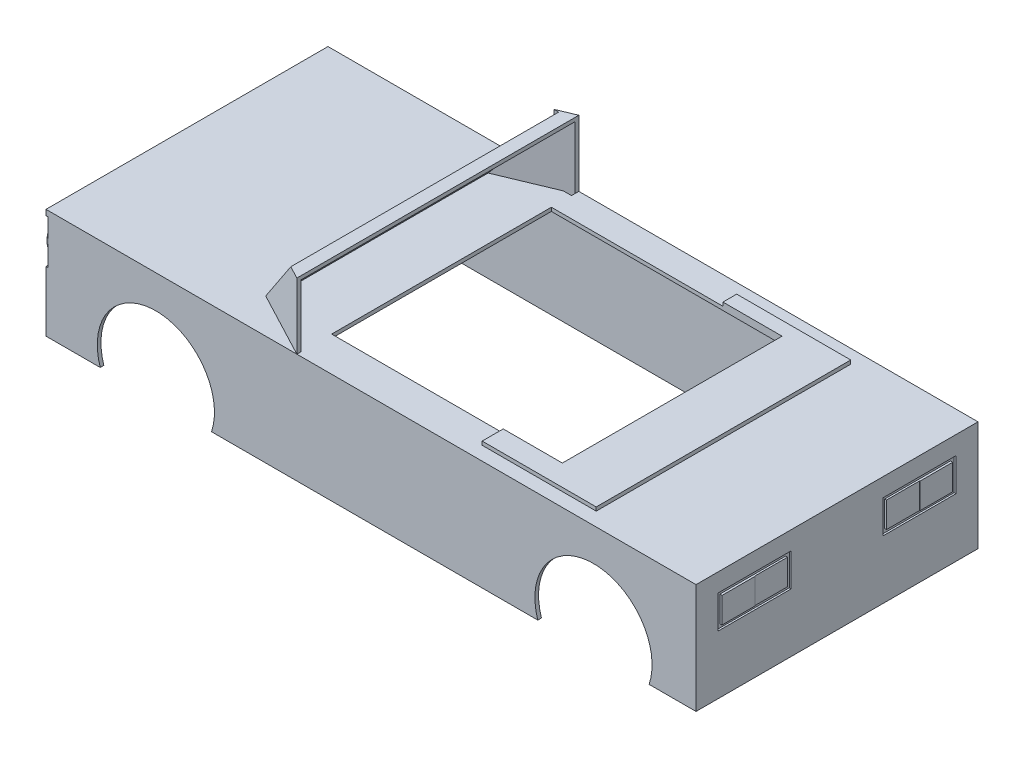
SolidWorks part; units mm, degrees
ref_plane "Front Plane" through (0, 0, 0) normal (0, 0, 1) x (1, 0, 0)
ref_plane "Top Plane" through (0, 0, 0) normal (0, 1, 0) x (1, 0, 0)
ref_plane "Right Plane" through (0, 0, 0) normal (1, 0, 0) x (0, 0, -1)
sketch "Sketch1" plane through (0, 0, 0) normal (0, 0, 1) x (1, 0, 0)
  line L1 (-88.75, 15) -> (88.75, 15)
  line L2 (-88.75, 15) -> (-88.75, -15)
  line L3 (-88.75, -15) -> (88.75, -15)
  line L4 (88.75, 15) -> (88.75, -15)
  point P0 (0, 0)
  dimension "D1" = 177.5
  dimension "D2" = 30
extrude "Boss-Extrude1" add sketch "Sketch1" along normal blind 77
sketch "Sketch2" plane through (0, -15, 0) normal (0, -1, 0) x (1, 0, 0)
  line L0 (-88.75, 77) -> (88.75, 77) construction
  line L1 (-87.75, 76) -> (87.75, 76)
  line L2 (-87.75, 76) -> (-87.75, 3)
  line L3 (-87.75, 3) -> (87.75, 3)
  line L4 (87.75, 76) -> (87.75, 3)
  line L5 (-88.75, 77) -> (-88.75, 0) construction
  dimension "D1" = 175.5
  dimension "D2" = 73
  dimension "D3" = 1
  dimension "D4" = 1
extrude "Cut-Extrude1" cut sketch "Sketch2" against normal blind 29
sketch "Sketch3" plane through (0, 0, 77) normal (0, 0, 1) x (1, 0, 0)
  line L0 (88.75, 15) -> (-88.75, 15) construction
  line L1 (-88.75, 15) -> (-88.75, -15) construction
  line L2 (88.75, -15) -> (88.75, 15) construction
  circle A0 centre (-58.75, -10) radius 16
  circle A1 centre (60.75, -10) radius 16
  dimension "D1" = 32
  dimension "D2" = 25
  dimension "D3" = 25
  dimension "D4" = 30
  dimension "D5" = 28
extrude "Cut-Extrude2" cut sketch "Sketch3" against normal blind 1
sketch "Sketch4" plane through (0, 0, 0) normal (0, 0, -1) x (-1, 0, 0)
  line L0 (-88.75, 15) -> (88.75, 15) construction
  line L1 (88.75, 15) -> (88.75, -15) construction
  line L2 (-88.75, -15) -> (-88.75, 15) construction
  circle A0 centre (-60.75, -10) radius 16
  circle A1 centre (58.75, -10) radius 16
  dimension "D1" = 25
  dimension "D2" = 25
  dimension "D3" = 30
  dimension "D4" = 28
extrude "Cut-Extrude3" cut sketch "Sketch4" against normal blind 1
sketch "Sketch5" plane through (0, 15, 0) normal (0, 1, 0) x (1, 0, 0)
  line L1 (-20.25, -7.5) -> (42.75, -7.5)
  line L2 (-20.25, -7.5) -> (-20.25, -67.5)
  line L3 (-20.25, -67.5) -> (42.75, -67.5)
  line L4 (42.75, -7.5) -> (42.75, -67.5)
  line L5 (88.75, 0) -> (-88.75, 0) construction
  line L7 (88.75, -77) -> (88.75, 0) construction
  point P0 (11.25, -35)
  dimension "D1" = 63
  dimension "D2" = 60
  dimension "D3" = 7.5
  dimension "D4" = 46
extrude "Cut-Extrude4" cut sketch "Sketch5" against normal blind 1
sketch "Sketch6" plane through (0, 15, 0) normal (0, 1, 0) x (1, 0, 0)
  line L0 (88.75, 0) -> (-88.75, 0) construction
  line L1 (-20.25, 0) -> (-38.25, 0)
  line L2 (-20.25, 0) -> (-20.25, -77)
  line L3 (-20.25, -77) -> (-38.25, -77)
  line L4 (-38.25, 0) -> (-38.25, -77)
  line L5 (88.75, -77) -> (-88.75, -77) construction
  line L6 (-20.25, -7.5) -> (-20.25, -67.5) construction
  dimension "D1" = 18
extrude "Boss-Extrude2" add sketch "Sketch6" along normal blind 18
sketch "Sketch9" plane through (0, 33, 0) normal (0, 1, 0) x (1, 0, 0)
  line L0 (-20.25, 0) -> (-38.25, -7.5)
  line L1 (-38.25, 0) -> (-38.25, -77) construction
  line L2 (-38.25, -7.5) -> (-38.25, 0)
  line L3 (-38.25, 0) -> (-20.25, 0)
  line L4 (-20.25, -77) -> (-38.25, -77)
  line L5 (-38.25, -77) -> (-38.25, -67.5)
  line L6 (-38.25, 0) -> (-38.25, -77) construction
  line L7 (-38.25, -67.5) -> (-20.25, -77)
  dimension "D1" = 7.5
extrude "Cut-Extrude6" cut sketch "Sketch9" against normal blind 18
sketch "Sketch12" plane through (0, 0, 77) normal (0, 0, 1) x (1, 0, 0)
  line L0 (-23.75, 33) -> (-38.25, 15)
  line L1 (-20.25, 33) -> (-38.25, 33) construction
  line L2 (-38.25, 15) -> (-38.25, 33)
  line L3 (-38.25, 33) -> (-23.75, 33)
  dimension "D1" = 14.5
extrude "Cut-Extrude7" cut sketch "Sketch12" against normal blind 75
shell "Shell2" thickness 1 removed face at (-20.25, 19.25, 38)
sketch "Sketch13" plane through (0, 15, 0) normal (0, 1, 0) x (1, 0, 0)
  line L0 (88.75, 0) -> (-20.25, 0) construction
  line L1 (26.6038, -73.25) -> (57.75, -73.25)
  line L2 (26.6038, -73.25) -> (26.6038, -67.5)
  line L3 (26.6038, -3.75) -> (57.75, -3.75)
  line L4 (57.75, -73.25) -> (57.75, -3.75)
  line L5 (88.75, -77) -> (-20.25, -77) construction
  line L6 (42.75, -67.5) -> (42.75, -7.5) construction
  line L7 (42.75, -67.5) -> (26.6038, -67.5)
  line L8 (-20.25, -67.5) -> (42.75, -67.5) construction
  line L10 (42.75, -7.5) -> (-20.25, -7.5) construction
  line L11 (26.6038, -7.5) -> (42.75, -7.5)
  line L12 (42.75, -7.5) -> (42.75, -67.5)
  line L13 (26.6038, -7.5) -> (26.6038, -3.75)
  dimension "D1" = 3.75
  dimension "D2" = 3.75
  dimension "D3" = 15
extrude "Boss-Extrude3" add sketch "Sketch13" along normal blind 1
sketch "Sketch14" plane through (-88.75, 0, 0) normal (-1, 0, 0) x (0, 0, 1)
  line L0 (0, 15) -> (0, -15) construction
  line L1 (0, 13.5) -> (77, 13.5)
  line L2 (0, 13.5) -> (0, 1.5)
  line L3 (0, 1.5) -> (77, 1.5)
  line L4 (77, 13.5) -> (77, 1.5)
  line L5 (77, 15) -> (77, -15) construction
  line L6 (7.5, 15) -> (67.5, 15) construction
  dimension "D1" = 1.5
  dimension "D2" = 12
extrude "Cut-Extrude8" cut sketch "Sketch14" against normal blind 0.5
sketch "Sketch15" plane through (-88.25, 0, 0) normal (-1, 0, 0) x (0, 0, 1)
  line L0 (0, 13.5) -> (0, 1.5) construction
  line L1 (77, 1.5) -> (77, 13.5) construction
  circle A0 centre (6, 7.4792) radius 5.75
  circle A1 centre (71, 7.4792) radius 5.75
  circle A2 centre (18, 7.4792) radius 3.1185
  circle A3 centre (59, 7.4792) radius 3.1019
  dimension "D1" = 11.5
  dimension "D3" = 11.5
  dimension "D2" = 6
  dimension "D4" = 6
  dimension "D5" = 12
  dimension "D6" = 12
extrude "Boss-Extrude5" add sketch "Sketch15" along normal blind 0.5
sketch "Sketch16" plane through (-88.75, 0, 0) normal (-1, 0, 0) x (0, 0, 1)
  circle A0 centre (6, 7.4792) radius 5
  circle A1 centre (18, 7.4792) radius 2.5
  circle A2 centre (59, 7.4792) radius 2.5
  circle A3 centre (71, 7.4792) radius 5
  dimension "D1" = 10
  dimension "D2" = 10
  dimension "D3" = 5
  dimension "D4" = 5
extrude "Boss-Extrude6" add sketch "Sketch16" along normal blind 0.25
sketch "Sketch17" plane through (88.75, 0, 0) normal (1, 0, 0) x (0, 0, -1)
  line L0 (-77, -15) -> (-77, 15) construction
  line L1 (-71, 10) -> (-51, 10)
  line L2 (-71, 10) -> (-71, 1)
  line L3 (-71, 1) -> (-51, 1)
  line L4 (-51, 10) -> (-51, 1)
  line L5 (-26, 10) -> (-6, 10)
  line L6 (-26, 10) -> (-26, 1)
  line L7 (-26, 1) -> (-6, 1)
  line L8 (-6, 10) -> (-6, 1)
  line L9 (0, -15) -> (0, 15) construction
  line L10 (-73.25, 15) -> (-3.75, 15) construction
  dimension "D1" = 20
  dimension "D2" = 20
  dimension "D3" = 6
  dimension "D4" = 6
  dimension "D5" = 9
  dimension "D6" = 9
  dimension "D7" = 5
  dimension "D8" = 5
extrude "Cut-Extrude9" cut sketch "Sketch17" against normal blind 0.5
sketch "Sketch18" plane through (88.25, 0, 0) normal (1, 0, 0) x (0, 0, -1)
  line L1 (-70, 9) -> (-52, 9)
  line L2 (-70, 9) -> (-70, 2)
  line L3 (-70, 2) -> (-52, 2)
  line L4 (-52, 9) -> (-52, 2)
  line L5 (-25, 9) -> (-7, 9)
  line L6 (-25, 9) -> (-25, 2)
  line L7 (-25, 2) -> (-7, 2)
  line L8 (-7, 9) -> (-7, 2)
  line L10 (-71, 10) -> (-71, 1) construction
  line L11 (-51, 10) -> (-71, 10) construction
  line L12 (-6, 10) -> (-26, 10) construction
  line L13 (-26, 10) -> (-26, 1) construction
  dimension "D1" = 18
  dimension "D2" = 7
  dimension "D3" = 1
  dimension "D4" = 1
  dimension "D5" = 18
  dimension "D6" = 7
  dimension "D7" = 1
  dimension "D8" = 1
extrude "Boss-Extrude7" add sketch "Sketch18" along normal blind 0.5
sketch "Sketch19" plane through (88.75, 0, 0) normal (1, 0, 0) x (0, 0, -1)
  line L0 (-61, 9) -> (-61, 2)
  line L1 (-52, 9) -> (-70, 9) construction
  line L2 (-70, 2) -> (-52, 2) construction
  line L3 (-61, 2) -> (-70, 2)
  line L4 (-70, 2) -> (-70, 9)
  line L5 (-70, 9) -> (-61, 9)
  line L6 (-16, 9) -> (-7, 9)
  line L7 (-7, 9) -> (-25, 9) construction
  line L8 (-7, 9) -> (-7, 2)
  line L9 (-7, 2) -> (-16, 2)
  line L10 (-25, 2) -> (-7, 2) construction
  line L11 (-16, 2) -> (-16, 9)
extrude "Boss-Extrude8" add sketch "Sketch19" along normal blind 0.1
